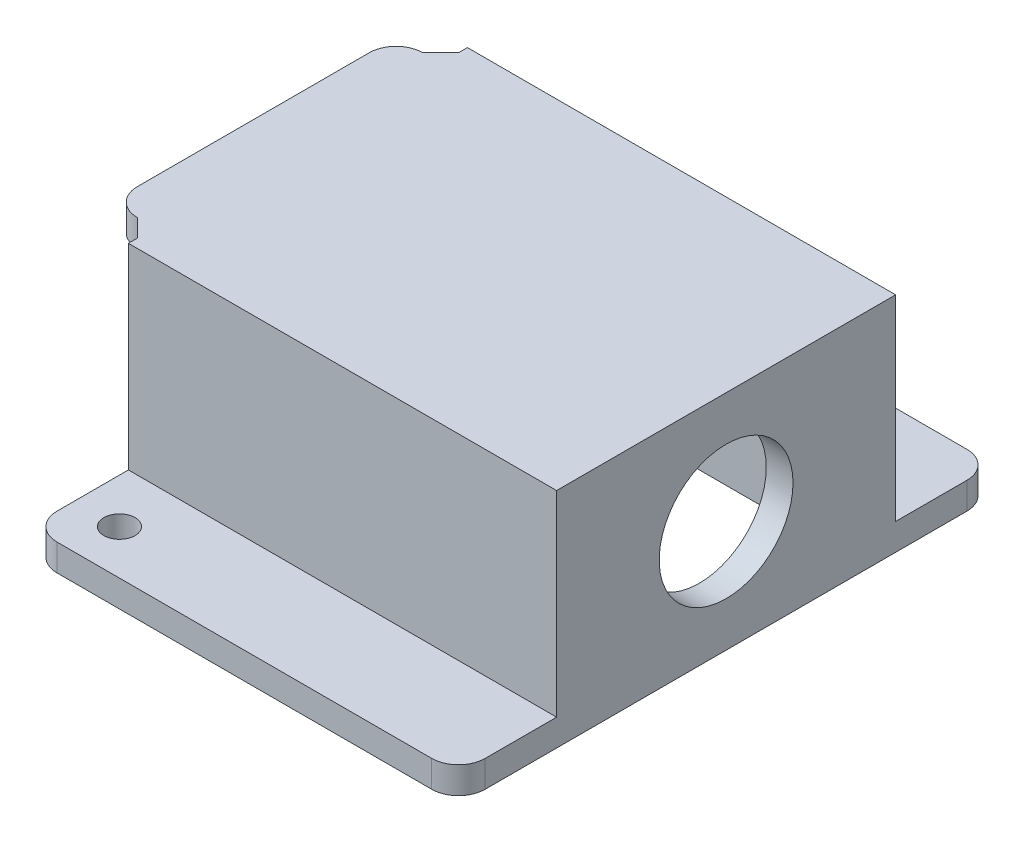
SolidWorks part; units mm, degrees
ref_plane "前视基准面" through (0, 0, 0) normal (0, 0, 1) x (1, 0, 0)
ref_plane "上视基准面" through (0, 0, 0) normal (0, 1, 0) x (1, 0, 0)
ref_plane "右视基准面" through (0, 0, 0) normal (1, 0, 0) x (0, 0, -1)
other "Configuration Table"
sketch "草图1" plane through (0, 0, 0) normal (0, 1, 0) x (1, 0, 0)
  line L1 (0, 0) -> (53, 0)
  line L2 (0, 0) -> (0, 60)
  line L3 (0, 60) -> (53, 60)
  line L4 (53, 0) -> (53, 60)
  dimension "D1" = 60
  dimension "D2" = 53
extrude "凸台-拉伸1" add sketch "草图1" along normal blind 3
sketch "草图2" plane through (0, 3, 0) normal (0, 1, 0) x (1, 0, 0)
  line L0 (0, 49) -> (53, 49)
  line L1 (0, 60) -> (0, 0) construction
  line L2 (53, 49) -> (53, 11)
  line L3 (53, 11) -> (0, 11)
  line L4 (0, 11) -> (0, 14)
  line L5 (0, 14) -> (50, 14)
  line L6 (50, 14) -> (50, 46)
  line L7 (50, 46) -> (0, 46)
  line L8 (0, 46) -> (0, 49)
  line L9 (0, 49) -> (0, 60) construction
  line L10 (0, 11) -> (0, 0) construction
  dimension "D1" = 3
  dimension "D2" = 3
  dimension "D3" = 32
  dimension "D4" = 3
  dimension "D5" = 50
extrude "凸台-拉伸2" add sketch "草图2" along normal blind 22
sketch "草图3" plane through (50, 0, 0) normal (-1, 0, 0) x (0, 0, 1)
  line L0 (-14, 25) -> (-14, 3) construction
  line L1 (-46, 25) -> (-14, 25)
  line L2 (-46, 25) -> (-46, 22)
  line L3 (-46, 22) -> (-14, 22)
  line L4 (-14, 25) -> (-14, 22)
  dimension "D1" = 3
extrude "凸台-拉伸3" add sketch "草图3" along normal blind 50
sketch "草图4" plane through (0, 0, 0) normal (-1, 0, 0) x (0, 0, 1)
sketch "草图5" plane through (0, 0, 0) normal (-1, 0, 0) x (0, 0, 1)
  line L0 (-49, 25) -> (-49, 3)
  line L1 (-49, 3) -> (-60, 3)
  line L2 (-60, 3) -> (-60, 0)
  line L3 (-60, 0) -> (0, 0)
  line L4 (0, 0) -> (0, 3)
  line L5 (0, 3) -> (-11, 3)
  line L6 (-11, 3) -> (-11, 25)
  line L7 (-11, 25) -> (-14, 25)
  line L8 (-49, 25) -> (-11, 25) construction
  line L9 (-14, 25) -> (-14, 22)
  line L10 (-14, 22) -> (-46, 22)
  line L11 (-46, 22) -> (-46, 25)
  line L12 (-46, 25) -> (-49, 25)
extrude "切除-拉伸1" cut sketch "草图5" against normal blind 5
sketch "草图6" plane through (5, 0, 0) normal (-1, 0, 0) x (0, 0, 1)
  line L0 (-60, 0) -> (0, 0) construction
  line L1 (-46, 3) -> (-14, 3)
  line L2 (-46, 3) -> (-46, 0)
  line L3 (-46, 0) -> (-14, 0)
  line L4 (-14, 3) -> (-14, 0)
  dimension "D1" = 32
extrude "切除-拉伸2" cut sketch "草图6" against normal blind 45
sketch "草图7" plane through (53, 0, 0) normal (1, 0, 0) x (0, 0, -1)
  line L0 (30, 12.5) -> (11, 12.5) construction
  line L1 (11, 25) -> (11, 3) construction
  line L2 (30, 12.5) -> (49, 12.5) construction
  line L3 (49, 25) -> (49, 3) construction
  line L4 (30, 12.5) -> (30, 25) construction
  line L5 (11, 25) -> (49, 25) construction
  line L6 (30, 12.5) -> (30, 0) construction
  line L7 (0, 0) -> (60, 0) construction
  circle A0 centre (30, 12.5) radius 7.5
  dimension "D1" = 15
extrude "切除-拉伸3" cut sketch "草图7" against normal blind 45
sketch "草图8" plane through (0, 0, 0) normal (0, -1, 0) x (1, 0, 0)
  line L0 (10, -5) -> (10, 0) construction
  line L1 (5, 0) -> (53, 0) construction
  line L2 (10, -55) -> (10, -60) construction
  line L3 (53, -60) -> (5, -60) construction
  line L4 (5, -14) -> (5, 0) construction
  line L6 (5, -60) -> (5, -46) construction
  circle A0 centre (10, -5) radius 1.75
  circle A1 centre (10, -55) radius 1.75
  dimension "D1" = 3.5
  dimension "D2" = 3.5
  dimension "D3" = 50
  dimension "D4" = 5
  dimension "D5" = 5
extrude "切除-拉伸4" cut sketch "草图8" against normal blind 45
fillet "圆角1" radius 3 6 edges at (0, 23.5, -14) (0, 23.5, -46) (5, 1.5, -60) (53, 1.5, -60) (53, 1.5, 0) (5, 1.5, 0)
chamfer "倒角1" distance 2 angle 45 2 edges at (5, 23.5, -46) (5, 23.5, -14)
